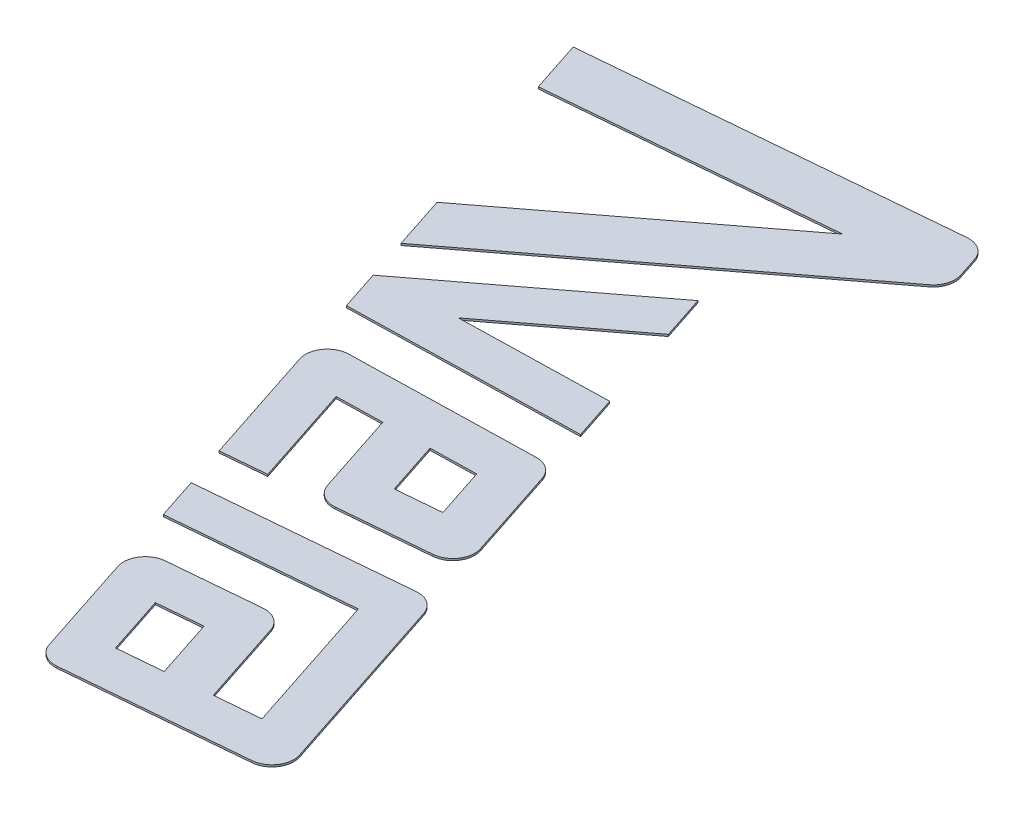
SolidWorks part; units mm, degrees
ref_plane "Front Plane" through (0, 0, 0) normal (0, 0, 1) x (1, 0, 0)
ref_plane "Top Plane" through (0, 0, 0) normal (0, 1, 0) x (1, 0, 0)
ref_plane "Right Plane" through (0, 0, 0) normal (1, 0, 0) x (0, 0, -1)
sketch "Sketch1" plane through (0, 0, 0) normal (0, 1, 0) x (1, 0, 0)
  line L0 (6.2636, 13.3847) -> (6.9802, 11.1991) construction
  line L2 (6.9802, 11.1991) -> (16.6844, 18.5822)
  line L4 (6.9802, 11.1991) -> (7.6656, 9.1086)
  line L5 (19.6969, 9.3941) -> (20.4135, 7.2086) construction
  line L6 (7.6656, 9.1086) -> (19.6969, 9.3941)
  line L10 (7.6656, 9.1086) -> (8.3822, 6.9231) construction
  line L11 (19.5596, 7.1883) -> (9.93, 6.9598)
  line L15 (19.6969, 9.3941) -> (18.9484, 11.677)
  line L20 (11.1641, 11.4923) -> (18.9484, 11.677)
  line L21 (11.1641, 11.4923) -> (17.4428, 16.2692)
  line L26 (11.5324, 4.6972) -> (13.2849, -0.6478)
  line L27 (17.4428, 16.2692) -> (16.6844, 18.5822)
  line L32 (13.0803, 4.7339) -> (11.5324, 4.6972)
  line L39 (5.3404, 16.2005) -> (2.7423, 24.1247) construction
  line L45 (17.2762, 2.0125) -> (16.3584, 4.8117)
  line L46 (13.2849, -0.6478) -> (10.9324, -0.855)
  line L56 (13.0821, -7.4116) -> (20.1616, -6.7881) construction
  line L58 (6.2636, 13.3847) -> (5.3404, 16.2005)
  line L59 (17.4595, 25.4208) -> (5.3404, 16.2005)
  line L60 (13.0821, -7.4116) -> (15.5745, -15.0134) construction
  line L61 (15.5745, -15.0134) -> (27.3591, -13.9756) construction
  line L62 (20.4135, 7.2086) -> (8.3822, 6.9231) construction
  line L64 (20.4135, 7.2086) -> (22.717, 0.1828) construction
  line L65 (8.8645, 5.4519) -> (10.9324, -0.855)
  line L66 (18.7602, 4.8687) -> (16.3584, 4.8117)
  line L68 (20.6796, 6.3969) -> (22.2656, 1.5595)
  line L69 (14.2003, 3.9425) -> (15.3531, 0.4267)
  line L71 (18.7602, 4.8687) -> (19.6287, 2.2197)
  line L72 (19.6287, 2.2197) -> (17.2762, 2.0125)
  line L73 (21.2738, 0.0557) -> (16.5467, -0.3606)
  line L74 (22.717, 0.1828) -> (10.9324, -0.855) construction
  line L75 (18.7602, 4.8687) -> (8.4367, 4.6237) construction
  line L76 (11.6489, -3.0405) -> (12.3655, -5.2261)
  line L77 (19.6287, 2.2197) -> (10.7306, 1.4361) construction
  line L78 (10.9324, -0.855) -> (11.6489, -3.0405) construction
  line L79 (11.6489, -3.0405) -> (22.5243, -2.0828)
  line L80 (12.3655, -5.2261) -> (21.7976, -4.3954)
  line L81 (23.718, -2.8701) -> (26.9077, -12.5989)
  line L82 (21.7976, -4.3954) -> (24.2708, -11.9387)
  line L83 (12.3655, -5.2261) -> (13.0821, -7.4116) construction
  line L84 (20.446, -7.6555) -> (21.9183, -12.1459)
  line L85 (14.5253, -7.2845) -> (19.2524, -6.8682)
  line L86 (13.5335, -8.7884) -> (15.2901, -14.1461)
  line L87 (16.4837, -14.9334) -> (25.9159, -14.1027)
  line L88 (21.2481, -2.7193) -> (25.1736, -14.6922) construction
  line L89 (17.1912, -12.5622) -> (19.5438, -12.355)
  line L90 (23.4336, -2.0027) -> (27.3591, -13.9756) construction
  line L91 (15.3727, -12.7223) -> (27.1574, -11.6845) construction
  line L92 (16.1704, -9.4485) -> (17.1912, -12.5622)
  line L93 (16.1704, -9.4485) -> (18.5229, -9.2414)
  line L95 (16.1704, -9.4485) -> (17.76, -14.2969) construction
  line L96 (18.5449, -9.2394) -> (19.7327, -12.8624) construction
  line L97 (21.9183, -12.1459) -> (24.2708, -11.9387)
  line L98 (1.8466, 26.8566) -> (2.7423, 24.1247)
  line L99 (16.1704, -9.4485) -> (18.5449, -9.2394) construction
  line L100 (18.5229, -9.2414) -> (19.5438, -12.355)
  line L101 (20.1616, -6.7881) -> (21.9183, -12.1459) construction
  line L102 (14.2003, 3.9425) -> (13.9342, 4.7542)
  line L103 (13.0803, 4.7339) -> (13.9342, 4.7542)
  line L104 (15.2901, -14.1461) -> (17.5856, -21.1472) construction
  line L105 (17.4595, 25.4208) -> (2.7423, 24.1247)
  line L106 (22.4342, 26.6593) -> (22.0779, 27.746)
  line L107 (22.0377, 25.3858) -> (6.2636, 13.3847)
  line L108 (17.5856, -21.1472) -> (27.4307, -20.2802) construction
  line L109 (20.8842, 28.5333) -> (1.8466, 26.8566)
  line L110 (21.9183, -12.1459) -> (25.2554, -22.324) construction
  line L111 (17.5856, -21.1472) -> (19.4143, -26.7249) construction
  line L112 (19.4143, -26.7249) -> (29.6028, -25.8276) construction
  line L113 (25.2554, -22.324) -> (26.4939, -26.1014) construction
  arc A0 (14.5253, -7.2845) -> (13.5335, -8.7884) centre (14.6262, -8.4301) ccw
  arc A1 (16.4837, -14.9334) -> (15.2901, -14.1461) centre (16.3829, -13.7878) cw
  arc A2 (22.0377, 25.3858) -> (22.4342, 26.6593) centre (21.3414, 26.301) ccw
  arc A3 (22.0779, 27.746) -> (20.8842, 28.5333) centre (20.9851, 27.3877) ccw
  arc A5 (9.93, 6.9598) -> (8.8645, 5.4519) centre (9.9573, 5.8101) ccw
  arc A6 (19.5596, 7.1883) -> (20.6796, 6.3969) centre (19.5868, 6.0387) cw
  arc A7 (25.9159, -14.1027) -> (26.9077, -12.5989) centre (25.815, -12.9572) ccw
  arc A8 (23.718, -2.8701) -> (22.5243, -2.0828) centre (22.6252, -3.2284) ccw
  arc A9 (16.5467, -0.3606) -> (15.3531, 0.4267) centre (16.4458, 0.785) cw
  arc A10 (21.2738, 0.0557) -> (22.2656, 1.5595) centre (21.1729, 1.2013) ccw
  arc A11 (19.2524, -6.8682) -> (20.446, -7.6555) centre (19.3533, -8.0138) cw
  dimension "D1" = 1.15
  dimension "D2" = 1.15
extrude "Boss-Extrude1" add sketch "Sketch1" along normal blind 0.1
